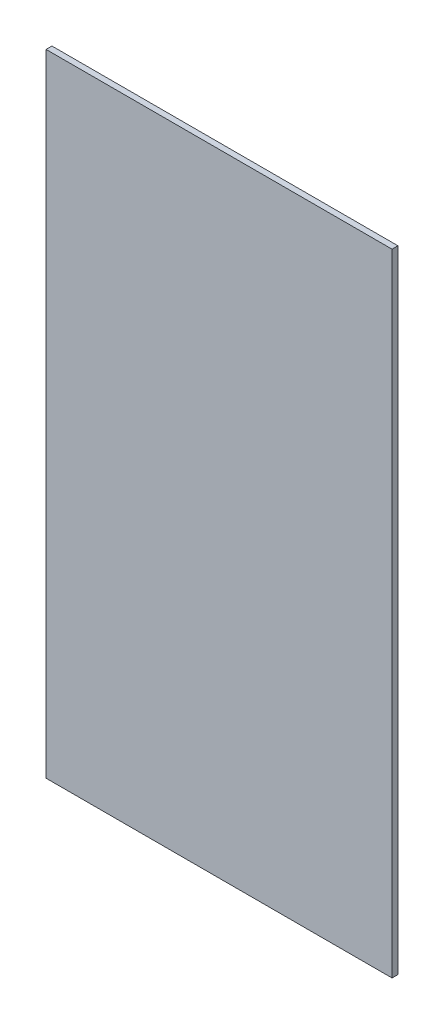
SolidWorks part; units mm, degrees
ref_plane "Front Plane" through (0, 0, 0) normal (0, 0, 1) x (1, 0, 0)
ref_plane "Top Plane" through (0, 0, 0) normal (0, 1, 0) x (1, 0, 0)
ref_plane "Right Plane" through (0, 0, 0) normal (1, 0, 0) x (0, 0, -1)
sketch "Sketch1" plane through (0, 0, 0) normal (0, 0, 1) x (1, 0, 0)
  line L0 (-284.5572, -25.8475) -> (-132.1572, -25.8475) construction
  line L1 (-99.8992, -25.8475) -> (49.2125, -25.8475)
  line L2 (-99.8992, -25.8475) -> (-99.8992, -297.8658)
  line L3 (-99.8992, -297.8658) -> (49.2125, -297.8658)
  line L4 (49.2125, -25.8475) -> (49.2125, -297.8658)
extrude "Boss-Extrude1" add sketch "Sketch1" along normal blind 2.54
